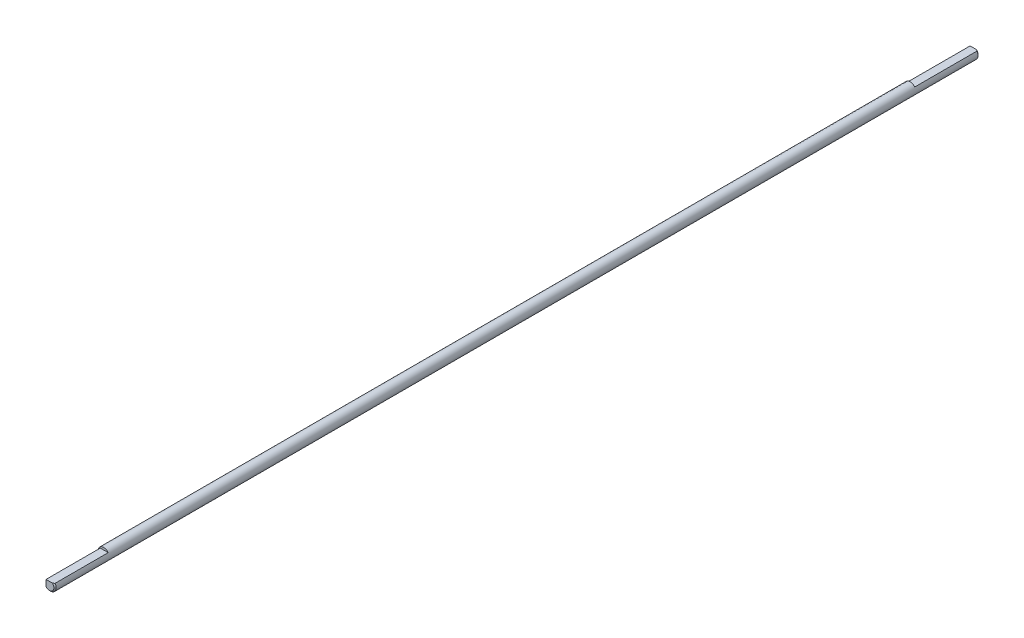
SolidWorks part; units mm, degrees
material "AISI 1020"
ref_plane "Спереди" through (0, 0, 0) normal (0, 0, 1) x (1, 0, 0)
ref_plane "Сверху" through (0, 0, 0) normal (0, 1, 0) x (1, 0, 0)
ref_plane "Справа" through (0, 0, 0) normal (1, 0, 0) x (0, 0, -1)
sketch "Эскиз1" plane through (0, 0, 0) normal (0, 0, 1) x (1, 0, 0)
  circle A0 centre (0, 0) radius 2.5
  dimension "D1" = 5
extrude "Body" add sketch "Эскиз1" along normal blind 408.5
chamfer "ChamferEdges" distance 0.5 angle 45 2 edges at (2.5, 0, 408.5) (2.5, 0, 0)
sketch "Sketch2" plane through (0, 0, 0) normal (1, 0, 0) x (0, 0, -1)
  line L0 (-408.5, 2) -> (-408.5, -2) construction
  line L1 (-28, 4.0099) -> (0.6305, 4.0099)
  line L2 (-28, 4.0099) -> (-28, 1.5)
  line L3 (-28, 1.5) -> (0.6305, 1.5)
  line L4 (0.6305, 4.0099) -> (0.6305, 1.5)
  line L6 (-408, -2.5) -> (-0.5, -2.5) construction
  line L11 (-384.5, 3.4421) -> (-384.5, 1.5)
  line L13 (-412.5, 3.4421) -> (-384.5, 3.4421)
  line L14 (-412.5, 3.4421) -> (-412.5, 1.5)
  line L15 (-412.5, 1.5) -> (-384.5, 1.5)
  dimension "D1" = 28
  dimension "D2" = 4
  dimension "D4" = 24
extrude "FirstSlots" cut sketch "Sketch2" against normal through all both and the other way through all
pattern_circular "CirPattern1" count 2 every 90 about axis through (0, 0, 408.5) along (0, 0, 1) of "FirstSlots"
